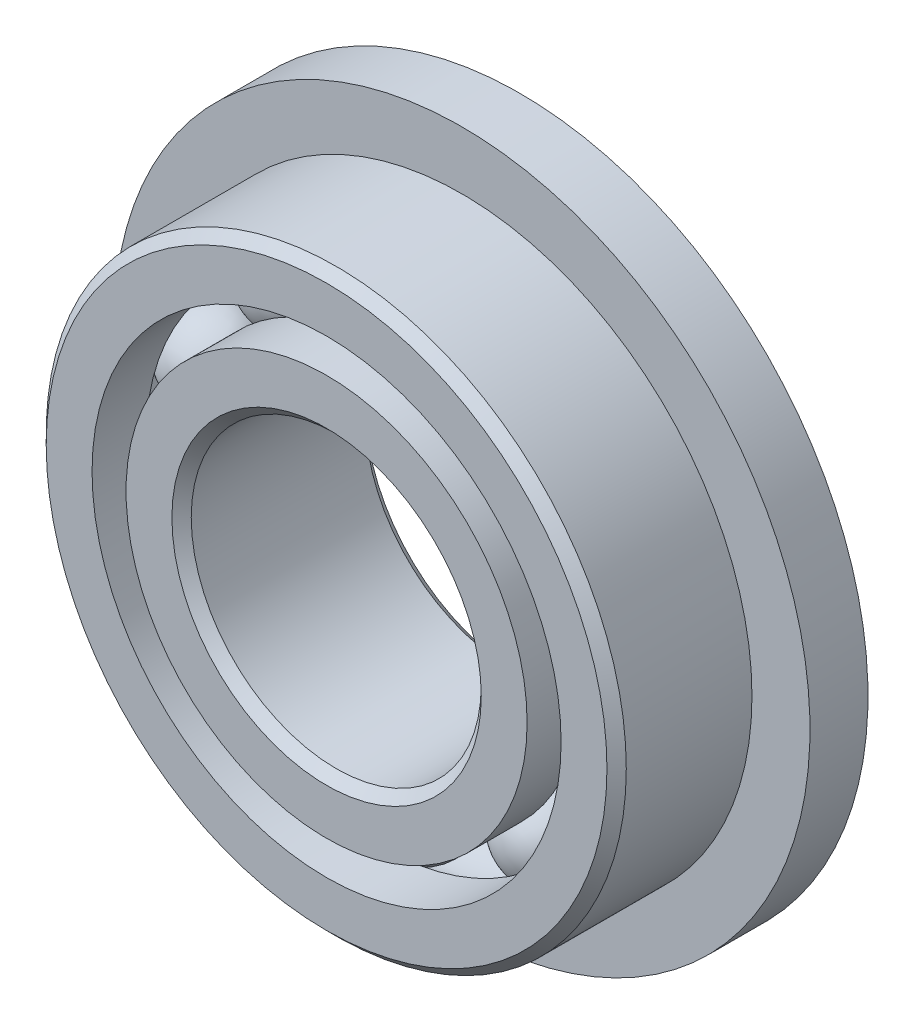
SolidWorks part; units mm, degrees
material "Stainless Steel (ferritic)"
ref_plane "Front Plane" through (0, 0, 0) normal (0, 0, 1) x (1, 0, 0)
ref_plane "Top Plane" through (0, 0, 0) normal (0, 1, 0) x (1, 0, 0)
ref_plane "Right Plane" through (0, 0, 0) normal (1, 0, 0) x (0, 0, -1)
sketch "Sketch1" plane through (0, 0, 0) normal (1, 0, 0) x (0, 0, -1)
  line L0 (-1, 0) -> (1, 0) construction
  line L1 (0, 3) -> (0, -3) construction
  line L2 (0.9, 3) -> (-0.9, 3)
  line L3 (-0.9, 3) -> (-1, 2.9)
  line L4 (-1, 2.9) -> (-1, 2.4258)
  line L5 (-1, 2.4258) -> (-0.4444, 2.4258)
  line L6 (1, 2.4258) -> (0.4444, 2.4258)
  line L7 (1, 2.9) -> (1, 2.4258)
  line L8 (0.9, 3) -> (1, 2.9)
  line L9 (0, 3) -> (0, 2.25) construction
  line L10 (0, 2.25) -> (0, 1.5) construction
  arc A0 (-0.4444, 2.4258) -> (0.4444, 2.4258) centre (0, 2.25) cw
  point P14 (0, 1.5)
  dimension "Width" = 2
  dimension "OD" = 6
  dimension "D1" = 45
  dimension "D2" = 0.1
  dimension "Shaft Dia" = 3
  dimension "D3" = 0.8889
  dimension "D4" = 0.1758
revolve "Revolve1" add sketch "Sketch1" angle 360 about L0
sketch "Sketch3" plane through (0, 0, 0) normal (1, 0, 0) x (0, 0, -1)
  line L0 (-1, 2.0742) -> (-0.4444, 2.0742)
  line L1 (0, 3) -> (0, -3) construction
  line L2 (-1, 2.9) -> (-1, 2.4258) construction
  line L3 (-1, 2.0742) -> (-1, 1.6)
  line L4 (-0.9, 3) -> (-1, 2.9) construction
  line L5 (-1, 1.6) -> (-0.9, 1.5)
  line L6 (-0.9, 1.5) -> (0.9, 1.5)
  line L7 (0.9, 3) -> (0.9, -3) construction
  line L8 (0.9, 1.5) -> (1, 1.6)
  line L9 (1, -2.9) -> (1, 2.9) construction
  line L10 (1, 1.6) -> (1, 2.0742)
  line L11 (1, 2.0742) -> (0.4444, 2.0742)
  line L13 (0.9, 3) -> (1, 2.9) construction
  arc A0 (0.4444, 2.4258) -> (-0.4444, 2.4258) centre (0, 2.25) ccw construction
  arc A1 (0.4444, 2.0742) -> (-0.4444, 2.0742) centre (0, 2.25) cw
revolve "Revolve3" add sketch "Sketch3" angle 360 about L0
sketch "Sketch4" plane through (0, 0, 0) normal (1, 0, 0) x (0, 0, -1)
  line L0 (-0.478, 2.25) -> (0.478, 2.25)
  arc A2 (-0.478, 2.25) -> (0.478, 2.25) centre (0, 2.25) cw
  arc A3 (0.4444, 2.4258) -> (-0.4444, 2.4258) centre (0, 2.25) ccw construction
revolve "Revolve4" add sketch "Sketch4" angle 360 about L0
ref_axis "Axis1" through (0, 0, -1) along (0, 0, 1)
pattern_circular "CirPattern1" count 10 every 36 about axis through (0, 0, -1) along (0, 0, 1) of bodies 104
sketch "Sketch5" plane through (0, 0, 0) normal (1, 0, 0) x (0, 0, -1)
  line L0 (-1, 2.4258) -> (-0.4444, 2.4258) construction
  line L1 (-0.95, 2.4258) -> (-0.478, 2.4258)
  line L2 (-0.95, 2.4258) -> (-0.95, 2.0742)
  line L3 (-0.95, 2.0742) -> (-0.478, 2.0742)
  line L4 (-0.478, 2.4258) -> (-0.478, 2.0742)
  line L5 (-1, 2.0742) -> (-0.4444, 2.0742) construction
  line L6 (1, 2.4258) -> (0.4444, 2.4258) construction
  line L7 (0.95, 2.4258) -> (0.478, 2.4258)
  line L8 (0.95, 2.4258) -> (0.95, 2.0742)
  line L9 (0.95, 2.0742) -> (0.478, 2.0742)
  line L10 (0.478, 2.4258) -> (0.478, 2.0742)
  line L11 (1, 2.0742) -> (0.4444, 2.0742) construction
  line L12 (-0.9, 3) -> (-1, 2.9) construction
  point P18 (-0.95, 2.95)
revolve "Revolve5" [suppressed] add sketch "Sketch5" angle 360 about L0
sketch "Sketch6" plane through (0, 0, 0) normal (1, 0, 0) x (0, 0, -1)
  line L0 (1, 0) -> (-1, 0) construction
  line L1 (1, 2.4258) -> (0.4, 2.4258)
  line L2 (1, 2.4258) -> (1, 3.6)
  line L3 (1, 3.6) -> (0.4, 3.6)
  line L4 (0.4, 2.4258) -> (0.4, 3.6)
  dimension "Th" = 0.6
  dimension "Flange OD" = 7.2
revolve "Revolve6" add sketch "Sketch6" angle 360 about L0
equation "\"D2@Sketch1\" = \"Width@Sketch1\"*.05"
equation "\"D3@Sketch1\" = \"Width@Sketch1\"/2.25"
equation "\"D4@Sketch1\" = (((\"OD@Sketch1\"-\"Width@Sketch1\")/2)/3.25)/3.5"
equation "\"D2@CirPattern1\" = 360/\"Balls@CirPattern1\""
